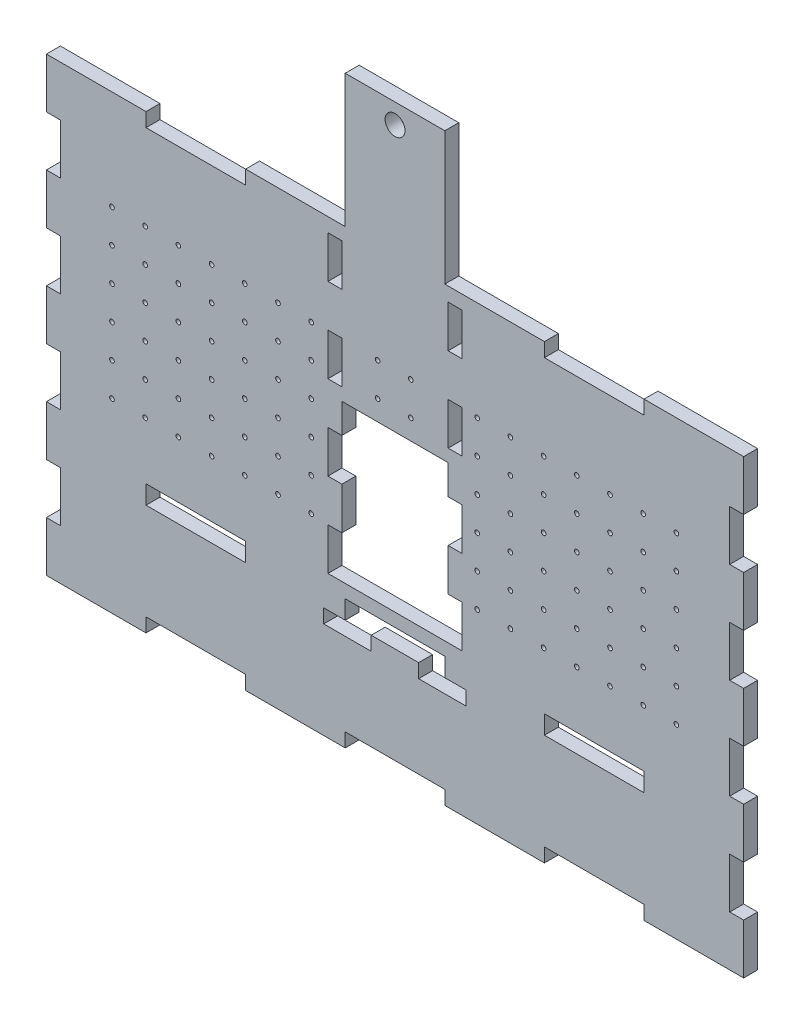
SolidWorks part; units mm, degrees
ref_plane "Front Plane" through (0, 0, 0) normal (0, 0, 1) x (1, 0, 0)
ref_plane "Top Plane" through (0, 0, 0) normal (0, 1, 0) x (1, 0, 0)
ref_plane "Right Plane" through (0, 0, 0) normal (1, 0, 0) x (0, 0, -1)
sketch "Sketch1" plane through (0, 0, 0) normal (0, 0, 1) x (1, 0, 0)
  line L1 (-127.8759, 88.4641) -> (138.8241, 88.4641)
  line L2 (-127.8759, 88.4641) -> (-127.8759, -84.2559)
  line L3 (-127.8759, -84.2559) -> (138.8241, -84.2559)
  line L4 (138.8241, 88.4641) -> (138.8241, -84.2559)
  dimension "D1" = 266.7
  dimension "D2" = 172.72
extrude "Boss-Extrude1" add sketch "Sketch1" along normal blind 5.334
sketch "Sketch2" plane through (0, 0, 5.334) normal (0, 0, 1) x (1, 0, 0)
  line L0 (-127.8759, -84.2559) -> (138.8241, -84.2559) construction
  line L1 (-89.7759, -84.2559) -> (-51.6759, -84.2559)
  line L2 (-89.7759, -84.2559) -> (-89.7759, -78.9219)
  line L3 (-89.7759, -78.9219) -> (-51.6759, -78.9219)
  line L4 (-51.6759, -84.2559) -> (-51.6759, -78.9219)
  line L5 (-89.7759, -78.9219) -> (-127.8759, -78.9219) construction
  line L6 (-13.5759, -84.2559) -> (24.5241, -84.2559)
  line L7 (-13.5759, -84.2559) -> (-13.5759, -78.9219)
  line L8 (-13.5759, -78.9219) -> (24.5241, -78.9219)
  line L9 (24.5241, -84.2559) -> (24.5241, -78.9219)
  line L10 (62.6241, -84.2559) -> (100.7241, -84.2559)
  line L11 (62.6241, -84.2559) -> (62.6241, -78.9219)
  line L12 (62.6241, -78.9219) -> (100.7241, -78.9219)
  line L13 (100.7241, -84.2559) -> (100.7241, -78.9219)
  line L14 (-127.8759, 88.4641) -> (-127.8759, -84.2559) construction
  line L15 (-51.6759, -78.9219) -> (-13.5759, -78.9219) construction
  line L16 (24.5241, -78.9219) -> (62.6241, -78.9219) construction
  line L17 (62.6241, -78.9219) -> (62.364, -79.7896) construction
  line L18 (100.7241, -78.9219) -> (138.8241, -78.9219) construction
  line L19 (138.8241, -84.2559) -> (138.8241, 88.4641) construction
  line L20 (-127.8759, 2.1041) -> (138.8241, 2.1041) construction
  line L21 (100.7241, 88.4641) -> (100.7241, 83.1301)
  line L22 (62.6241, 83.1301) -> (100.7241, 83.1301)
  line L23 (62.6241, 88.4641) -> (62.6241, 83.1301)
  line L24 (24.5241, 88.4641) -> (24.5241, 83.1301)
  line L25 (-13.5759, 83.1301) -> (24.5241, 83.1301)
  line L26 (-13.5759, 88.4641) -> (-13.5759, 83.1301)
  line L27 (-51.6759, 88.4641) -> (-51.6759, 83.1301)
  line L28 (-89.7759, 83.1301) -> (-51.6759, 83.1301)
  line L29 (-89.7759, 88.4641) -> (-89.7759, 83.1301)
  line L30 (62.6241, 88.4641) -> (100.7241, 88.4641)
  line L31 (-13.5759, 88.4641) -> (24.5241, 88.4641)
  line L32 (-89.7759, 88.4641) -> (-51.6759, 88.4641)
  dimension "D1" = 5.334
extrude "Cut-Extrude1" cut sketch "Sketch2" against normal through all
sketch "Sketch5" plane through (0, 0, 5.334) normal (0, 0, 1) x (1, 0, 0)
  line L0 (-51.6759, -34.8224) -> (-13.5759, -34.8224) construction
  line L1 (-89.7759, -34.8224) -> (-51.6759, -34.8224)
  line L2 (-89.7759, -34.8224) -> (-89.7759, -41.9344)
  line L3 (-89.7759, -41.9344) -> (-51.6759, -41.9344)
  line L4 (-51.6759, -34.8224) -> (-51.6759, -41.9344)
  line L5 (-13.5759, -34.8224) -> (24.5241, -34.8224)
  line L6 (-13.5759, -34.8224) -> (-13.5759, -41.9344)
  line L7 (-13.5759, -41.9344) -> (24.5241, -41.9344)
  line L8 (24.5241, -34.8224) -> (24.5241, -41.9344)
  line L9 (62.6241, -34.8224) -> (100.7241, -34.8224)
  line L10 (62.6241, -34.8224) -> (62.6241, -41.9344)
  line L11 (62.6241, -41.9344) -> (100.7241, -41.9344)
  line L12 (100.7241, -34.8224) -> (100.7241, -41.9344)
  line L13 (-51.6759, -41.9344) -> (-13.5759, -41.9344) construction
  line L14 (24.5241, -34.8224) -> (62.6241, -34.8224) construction
  line L15 (24.5241, -41.9344) -> (62.6241, -41.9344) construction
  line L16 (-89.7759, -34.8224) -> (-127.8759, -34.8224) construction
  line L17 (-127.8759, 88.4641) -> (-127.8759, -84.2559) construction
  line L18 (-89.7759, -41.9344) -> (-127.8759, -41.9344) construction
  line L19 (100.7241, -34.8224) -> (138.8241, -34.8224) construction
  line L20 (138.8241, -84.2559) -> (138.8241, 88.4641) construction
  line L21 (100.7241, -41.9344) -> (138.8241, -41.9344) construction
  dimension "D1" = 7.112
extrude "Cut-Extrude3" cut sketch "Sketch5" against normal through all
sketch "Sketch8" plane through (0, 0, 5.334) normal (0, 0, 1) x (1, 0, 0)
  line L0 (-13.5759, -41.9344) -> (24.5241, -41.9344) construction
  line L1 (-21.7977, -47.2684) -> (-3.6478, -47.2684)
  line L2 (-21.7977, -47.2684) -> (-21.7977, -41.9344)
  line L3 (-21.7977, -41.9344) -> (-3.6478, -41.9344)
  line L4 (-3.6478, -47.2684) -> (-3.6478, -41.9344)
  line L5 (-3.6478, -47.2684) -> (14.5022, -47.2684) construction
  line L6 (14.5022, -41.9344) -> (32.6521, -41.9344)
  line L7 (14.5022, -41.9344) -> (14.5022, -47.2684)
  line L8 (14.5022, -47.2684) -> (32.6521, -47.2684)
  line L9 (32.6521, -41.9344) -> (32.6521, -47.2684)
  line L10 (14.5022, -47.2684) -> (14.3218, -49.4005) construction
  line L11 (14.5022, -41.9344) -> (-3.6478, -41.9344) construction
  line L12 (62.6241, -34.8224) -> (62.6241, -41.9344) construction
  line L13 (-51.6759, -41.9344) -> (-51.6759, -34.8224) construction
  dimension "D1" = 5.334
  dimension "D2" = 29.972
  dimension "D3" = 29.8782
extrude "Cut-Extrude6" cut sketch "Sketch8" against normal through all
sketch "Sketch9" plane through (0, 0, 5.334) normal (0, 0, 1) x (1, 0, 0)
  line L0 (-127.8759, 88.4641) -> (-127.8759, -84.2559) construction
  line L1 (-127.8759, -65.0647) -> (-122.5419, -65.0647)
  line L2 (-127.8759, -65.0647) -> (-127.8759, -45.8736)
  line L3 (-127.8759, -45.8736) -> (-122.5419, -45.8736)
  line L4 (-122.5419, -65.0647) -> (-122.5419, -45.8736)
  line L5 (-122.5419, 69.273) -> (-122.5419, 88.4641) construction
  line L6 (-127.8759, -26.6825) -> (-122.5419, -26.6825)
  line L7 (-127.8759, -26.6825) -> (-127.8759, -7.4914)
  line L8 (-127.8759, -7.4914) -> (-122.5419, -7.4914)
  line L9 (-122.5419, -26.6825) -> (-122.5419, -7.4914)
  line L10 (-127.8759, 11.6997) -> (-122.5419, 11.6997)
  line L11 (-127.8759, 11.6997) -> (-127.8759, 30.8908)
  line L12 (-127.8759, 30.8908) -> (-122.5419, 30.8908)
  line L13 (-122.5419, 11.6997) -> (-122.5419, 30.8908)
  line L14 (-127.8759, 50.0819) -> (-122.5419, 50.0819)
  line L15 (-127.8759, 50.0819) -> (-127.8759, 69.273)
  line L16 (-127.8759, 69.273) -> (-122.5419, 69.273)
  line L17 (-122.5419, 50.0819) -> (-122.5419, 69.273)
  line L18 (-89.7759, 88.4641) -> (-127.8759, 88.4641) construction
  line L19 (-122.5419, 50.0819) -> (-122.5419, 30.8908) construction
  line L20 (-122.5419, 11.6997) -> (-122.5419, -7.4914) construction
  line L21 (-122.5419, -26.6825) -> (-122.5419, -45.8736) construction
  line L22 (-122.5419, -65.0647) -> (-122.5419, -84.2559) construction
  line L23 (-127.8759, -84.2559) -> (-89.7759, -84.2559) construction
  line L24 (5.4741, 83.1301) -> (5.4741, -78.9219) construction
  line L25 (-13.5759, 83.1301) -> (24.5241, 83.1301) construction
  line L26 (24.5241, -78.9219) -> (-13.5759, -78.9219) construction
  line L27 (133.4901, -65.0647) -> (133.4901, -84.2559) construction
  line L28 (133.4901, -26.6825) -> (133.4901, -45.8736) construction
  line L29 (133.4901, 11.6997) -> (133.4901, -7.4914) construction
  line L30 (133.4901, 50.0819) -> (133.4901, 30.8908) construction
  line L31 (133.4901, 69.273) -> (133.4901, 88.4641) construction
  line L32 (133.4901, 50.0819) -> (133.4901, 69.273)
  line L33 (138.8241, 69.273) -> (133.4901, 69.273)
  line L34 (138.8241, 50.0819) -> (138.8241, 69.273)
  line L35 (138.8241, 50.0819) -> (133.4901, 50.0819)
  line L36 (133.4901, 11.6997) -> (133.4901, 30.8908)
  line L37 (138.8241, 30.8908) -> (133.4901, 30.8908)
  line L38 (138.8241, 11.6997) -> (138.8241, 30.8908)
  line L39 (138.8241, 11.6997) -> (133.4901, 11.6997)
  line L40 (133.4901, -26.6825) -> (133.4901, -7.4914)
  line L41 (138.8241, -7.4914) -> (133.4901, -7.4914)
  line L42 (138.8241, -26.6825) -> (138.8241, -7.4914)
  line L43 (138.8241, -26.6825) -> (133.4901, -26.6825)
  line L44 (133.4901, -65.0647) -> (133.4901, -45.8736)
  line L45 (138.8241, -45.8736) -> (133.4901, -45.8736)
  line L46 (138.8241, -65.0647) -> (138.8241, -45.8736)
  line L47 (138.8241, -65.0647) -> (133.4901, -65.0647)
  dimension "D1" = 5.334
extrude "Cut-Extrude7" cut sketch "Sketch9" against normal through all
sketch "Sketch10" plane through (0, 88.4641, 0) normal (0, 1, 0) x (1, 0, 0)
  line L1 (24.5241, -5.334) -> (62.6241, -5.334)
  line L2 (24.5241, -5.334) -> (24.5241, 0)
  line L3 (24.5241, 0) -> (62.6241, 0)
  line L4 (62.6241, -5.334) -> (62.6241, 0)
extrude "Boss-Extrude2" add sketch "Sketch10" along normal blind 50.8
sketch "Sketch11" plane through (0, 0, 0) normal (0, 0, -1) x (-1, 0, 0)
  line L0 (-24.5241, 83.1301) -> (-24.5241, 139.2641) construction
  line L1 (-24.5241, 88.4641) -> (-31.1281, 88.4641)
  line L2 (-24.5241, 88.4641) -> (-24.5241, 129.1041)
  line L3 (-24.5241, 129.1041) -> (-31.1281, 129.1041)
  line L4 (-31.1281, 88.4641) -> (-31.1281, 129.1041)
  line L5 (13.5759, 88.4641) -> (51.6759, 88.4641) construction
  dimension "D1" = 6.604
  dimension "D2" = 40.64
  dimension "D3" = 0
extrude "Cut-Extrude8" cut sketch "Sketch11" against normal through all
sketch "Sketch12" plane through (0, 0, 5.334) normal (0, 0, 1) x (1, 0, 0)
  line L0 (62.6241, 139.2641) -> (62.6241, 83.1301) construction
  circle A0 centre (43.5741, 130.4765) radius 3.81
  dimension "D1" = 19.05
extrude "Cut-Extrude9" cut sketch "Sketch12" against normal through all
sketch "Sketch14" plane through (0, 0, 5.334) normal (0, 0, 1) x (1, 0, 0)
  line L0 (-89.7759, 88.4641) -> (-127.8759, 88.4641) construction
  circle A0 centre (-102.7976, 50.3641) radius 0.889
  circle A1 centre (-90.0976, 50.3641) radius 0.889
  circle A2 centre (-77.3976, 50.3641) radius 0.889
  circle A3 centre (-64.6976, 50.3641) radius 0.889
  circle A4 centre (-51.9976, 50.3641) radius 0.889
  circle A5 centre (-39.2976, 50.3641) radius 0.889
  circle A6 centre (-26.5976, 50.3641) radius 0.889
  circle A8 centre (-1.1976, 50.3641) radius 0.889
  circle A9 centre (11.5024, 50.3641) radius 0.889
  circle A11 centre (36.9024, 50.3641) radius 0.889
  circle A12 centre (49.6024, 50.3641) radius 0.889
  circle A13 centre (62.3024, 50.3641) radius 0.889
  circle A14 centre (75.0024, 50.3641) radius 0.889
  circle A15 centre (87.7024, 50.3641) radius 0.889
  circle A16 centre (100.4024, 50.3641) radius 0.889
  circle A17 centre (113.1024, 50.3641) radius 0.889
  circle A18 centre (-102.7976, 37.6641) radius 0.889
  circle A19 centre (-90.0976, 37.6641) radius 0.889
  circle A20 centre (-77.3976, 37.6641) radius 0.889
  circle A21 centre (-64.6976, 37.6641) radius 0.889
  circle A22 centre (-51.9976, 37.6641) radius 0.889
  circle A23 centre (-39.2976, 37.6641) radius 0.889
  circle A24 centre (-26.5976, 37.6641) radius 0.889
  circle A26 centre (-1.1976, 37.6641) radius 0.889
  circle A27 centre (11.5024, 37.6641) radius 0.889
  circle A29 centre (36.9024, 37.6641) radius 0.889
  circle A30 centre (49.6024, 37.6641) radius 0.889
  circle A31 centre (62.3024, 37.6641) radius 0.889
  circle A32 centre (75.0024, 37.6641) radius 0.889
  circle A33 centre (87.7024, 37.6641) radius 0.889
  circle A34 centre (100.4024, 37.6641) radius 0.889
  circle A35 centre (113.1024, 37.6641) radius 0.889
  circle A36 centre (-102.7976, 24.9641) radius 0.889
  circle A37 centre (-90.0976, 24.9641) radius 0.889
  circle A38 centre (-77.3976, 24.9641) radius 0.889
  circle A39 centre (-64.6976, 24.9641) radius 0.889
  circle A40 centre (-51.9976, 24.9641) radius 0.889
  circle A41 centre (-39.2976, 24.9641) radius 0.889
  circle A42 centre (-26.5976, 24.9641) radius 0.889
  circle A44 centre (-1.1976, 24.9641) radius 0.889
  circle A45 centre (11.5024, 24.9641) radius 0.889
  circle A47 centre (36.9024, 24.9641) radius 0.889
  circle A48 centre (49.6024, 24.9641) radius 0.889
  circle A49 centre (62.3024, 24.9641) radius 0.889
  circle A50 centre (75.0024, 24.9641) radius 0.889
  circle A51 centre (87.7024, 24.9641) radius 0.889
  circle A52 centre (100.4024, 24.9641) radius 0.889
  circle A53 centre (113.1024, 24.9641) radius 0.889
  circle A54 centre (-102.7976, 12.2641) radius 0.889
  circle A55 centre (-90.0976, 12.2641) radius 0.889
  circle A56 centre (-77.3976, 12.2641) radius 0.889
  circle A57 centre (-64.6976, 12.2641) radius 0.889
  circle A58 centre (-51.9976, 12.2641) radius 0.889
  circle A59 centre (-39.2976, 12.2641) radius 0.889
  circle A60 centre (-26.5976, 12.2641) radius 0.889
  circle A65 centre (36.9024, 12.2641) radius 0.889
  circle A66 centre (49.6024, 12.2641) radius 0.889
  circle A67 centre (62.3024, 12.2641) radius 0.889
  circle A68 centre (75.0024, 12.2641) radius 0.889
  circle A69 centre (87.7024, 12.2641) radius 0.889
  circle A70 centre (100.4024, 12.2641) radius 0.889
  circle A71 centre (113.1024, 12.2641) radius 0.889
  circle A72 centre (-102.7976, -0.4359) radius 0.889
  circle A73 centre (-90.0976, -0.4359) radius 0.889
  circle A74 centre (-77.3976, -0.4359) radius 0.889
  circle A75 centre (-64.6976, -0.4359) radius 0.889
  circle A76 centre (-51.9976, -0.4359) radius 0.889
  circle A77 centre (-39.2976, -0.4359) radius 0.889
  circle A78 centre (-26.5976, -0.4359) radius 0.889
  circle A79 centre (-13.8976, -0.4359) radius 0.889
  circle A80 centre (-1.1976, -0.4359) radius 0.889
  circle A81 centre (11.5024, -0.4359) radius 0.889
  circle A82 centre (24.2024, -0.4359) radius 0.889
  circle A83 centre (36.9024, -0.4359) radius 0.889
  circle A84 centre (49.6024, -0.4359) radius 0.889
  circle A85 centre (62.3024, -0.4359) radius 0.889
  circle A86 centre (75.0024, -0.4359) radius 0.889
  circle A87 centre (87.7024, -0.4359) radius 0.889
  circle A88 centre (100.4024, -0.4359) radius 0.889
  circle A89 centre (113.1024, -0.4359) radius 0.889
  circle A90 centre (-102.7976, -13.1359) radius 0.889
  circle A91 centre (-90.0976, -13.1359) radius 0.889
  circle A92 centre (-77.3976, -13.1359) radius 0.889
  circle A93 centre (-64.6976, -13.1359) radius 0.889
  circle A94 centre (-51.9976, -13.1359) radius 0.889
  circle A95 centre (-39.2976, -13.1359) radius 0.889
  circle A96 centre (-26.5976, -13.1359) radius 0.889
  circle A97 centre (-13.8976, -13.1359) radius 0.889
  circle A98 centre (-1.1976, -13.1359) radius 0.889
  circle A99 centre (11.5024, -13.1359) radius 0.889
  circle A100 centre (24.2024, -13.1359) radius 0.889
  circle A101 centre (36.9024, -13.1359) radius 0.889
  circle A102 centre (49.6024, -13.1359) radius 0.889
  circle A103 centre (62.3024, -13.1359) radius 0.889
  circle A104 centre (75.0024, -13.1359) radius 0.889
  circle A105 centre (87.7024, -13.1359) radius 0.889
  circle A106 centre (100.4024, -13.1359) radius 0.889
  circle A107 centre (113.1024, -13.1359) radius 0.889
  circle A108 centre (-1.1976, 12.2641) radius 0.889 [skipped]
  circle A110 centre (11.5024, 12.2641) radius 0.889 [skipped]
  circle A116 centre (24.2024, 50.3641) radius 0.889 [skipped]
  circle A117 centre (-13.8976, 50.3641) radius 0.889 [skipped]
  dimension "D1" = 18
  dimension "D2" = 38.1
  dimension "D4" = 1.778
  dimension "D3" = 6
extrude "Cut-Extrude11" cut sketch "Sketch14" against normal through all
sketch "Sketch15" plane through (0, 0, 5.334) normal (0, 0, 1) x (1, 0, 0)
  line L1 (31.1281, 129.1041) -> (24.5241, 129.1041)
  line L2 (31.1281, 129.1041) -> (31.1281, 139.2641)
  line L3 (31.1281, 139.2641) -> (24.5241, 139.2641)
  line L4 (24.5241, 129.1041) -> (24.5241, 139.2641)
extrude "Cut-Extrude12" cut sketch "Sketch15" against normal through all
sketch "Sketch16" plane through (0, 0, 5.334) normal (0, 0, 1) x (1, 0, 0)
  line L0 (5.4741, 83.1301) -> (5.4741, -78.9219) construction
  line L1 (-14.8459, 29.9476) -> (25.7941, 29.9476)
  line L2 (-14.8459, 29.9476) -> (-14.8459, -29.7424)
  line L3 (-14.8459, -29.7424) -> (25.7941, -29.7424)
  line L4 (25.7941, 29.9476) -> (25.7941, -29.7424)
  line L5 (-13.5759, 83.1301) -> (24.5241, 83.1301) construction
  line L6 (24.5241, -78.9219) -> (-13.5759, -78.9219) construction
  line L7 (24.5241, -34.8224) -> (-13.5759, -34.8224) construction
  dimension "D1" = 59.69
  dimension "D2" = 40.64
  dimension "D3" = 20.32
  dimension "D4" = 5.08
extrude "Cut-Extrude13" cut sketch "Sketch16" against normal through all
sketch "Sketch17" plane through (0, 0, 5.334) normal (0, 0, 1) x (1, 0, 0)
  line L0 (-14.8459, 29.9476) -> (-14.8459, -29.7424) construction
  line L1 (-14.8459, -29.7424) -> (-20.1799, -29.7424)
  line L2 (-14.8459, -29.7424) -> (-14.8459, -13.6178)
  line L3 (-14.8459, -13.6178) -> (-20.1799, -13.6178)
  line L4 (-20.1799, -29.7424) -> (-20.1799, -13.6178)
  line L5 (-14.8459, 2.5069) -> (-20.1799, 2.5069)
  line L6 (-14.8459, 2.5069) -> (-14.8459, 18.6315)
  line L7 (-14.8459, 18.6315) -> (-20.1799, 18.6315)
  line L8 (-20.1799, 2.5069) -> (-20.1799, 18.6315)
  line L9 (-20.1799, -13.6178) -> (-20.1799, 2.5069) construction
  line L10 (-20.1799, 50.8808) -> (-14.8459, 50.8808)
  line L11 (-20.1799, 50.8808) -> (-20.1799, 34.7562)
  line L12 (-20.1799, 34.7562) -> (-14.8459, 34.7562)
  line L13 (-14.8459, 50.8808) -> (-14.8459, 34.7562)
  line L14 (-20.1799, 67.0055) -> (-14.8459, 67.0055)
  line L15 (-20.1799, 67.0055) -> (-20.1799, 83.1301)
  line L16 (-20.1799, 83.1301) -> (-14.8459, 83.1301)
  line L17 (-14.8459, 67.0055) -> (-14.8459, 83.1301)
  line L18 (-20.1799, 18.6315) -> (-20.1799, 34.7562) construction
  line L19 (-20.1799, 67.0055) -> (-20.1799, 50.8808) construction
  line L20 (5.4741, 83.1301) -> (5.4741, -78.9219) construction
  line L21 (-13.5759, 83.1301) -> (24.5241, 83.1301) construction
  line L22 (24.5241, -78.9219) -> (-13.5759, -78.9219) construction
  line L23 (31.1281, 67.0055) -> (31.1281, 50.8808) construction
  line L24 (31.1281, 18.6315) -> (31.1281, 34.7562) construction
  line L25 (31.1281, -13.6178) -> (31.1281, 2.5069) construction
  line L26 (25.7941, 67.0055) -> (25.7941, 83.1301)
  line L27 (31.1281, 83.1301) -> (25.7941, 83.1301)
  line L28 (31.1281, 67.0055) -> (31.1281, 83.1301)
  line L29 (31.1281, 67.0055) -> (25.7941, 67.0055)
  line L30 (25.7941, 50.8808) -> (25.7941, 34.7562)
  line L31 (31.1281, 34.7562) -> (25.7941, 34.7562)
  line L32 (31.1281, 50.8808) -> (31.1281, 34.7562)
  line L33 (31.1281, 50.8808) -> (25.7941, 50.8808)
  line L34 (31.1281, 2.5069) -> (31.1281, 18.6315)
  line L35 (25.7941, 18.6315) -> (31.1281, 18.6315)
  line L36 (25.7941, 2.5069) -> (25.7941, 18.6315)
  line L37 (25.7941, 2.5069) -> (31.1281, 2.5069)
  line L38 (31.1281, -29.7424) -> (31.1281, -13.6178)
  line L39 (25.7941, -13.6178) -> (31.1281, -13.6178)
  line L40 (25.7941, -29.7424) -> (25.7941, -13.6178)
  line L41 (25.7941, -29.7424) -> (31.1281, -29.7424)
  dimension "D1" = 0
  dimension "D2" = 5.334
  dimension "D3" = 5.334
  dimension "D4" = 5.334
extrude "Cut-Extrude14" cut sketch "Sketch17" against normal through all
sketch "Sketch18" plane through (0, 0, 5.334) normal (0, 0, 1) x (1, 0, 0)
  line L0 (24.5241, 83.1301) -> (24.5241, 148.9274) construction
  line L1 (31.1281, 139.2641) -> (62.6241, 139.2641) construction
  line L2 (-13.5759, 83.1301) -> (24.5241, 83.1301)
  line L3 (-13.5759, 83.1301) -> (-13.5759, 139.2641)
  line L4 (-13.5759, 139.2641) -> (24.5241, 139.2641)
  line L5 (24.5241, 83.1301) -> (24.5241, 139.2641)
  dimension "D1" = 0
extrude "Boss-Extrude3" add sketch "Sketch18" against normal blind 5.334
sketch "Sketch19" plane through (0, 0, 5.334) normal (0, 0, 1) x (1, 0, 0)
  line L1 (31.1281, 88.4641) -> (65.8849, 88.4641)
  line L2 (31.1281, 88.4641) -> (31.1281, 143.4078)
  line L3 (31.1281, 143.4078) -> (65.8849, 143.4078)
  line L4 (65.8849, 88.4641) -> (65.8849, 143.4078)
extrude "Cut-Extrude15" cut sketch "Sketch19" against normal through all
sketch "Sketch20" plane through (0, 0, 5.334) normal (0, 0, 1) x (1, 0, 0)
  line L0 (5.4741, 139.2641) -> (5.4741, 29.9476) construction
  line L1 (24.5241, 139.2641) -> (-13.5759, 139.2641) construction
  line L2 (25.7941, 29.9476) -> (-14.8459, 29.9476) construction
  circle A0 centre (5.4741, 131.6441) radius 3.81
  dimension "D1" = 7.62
  dimension "D3" = 7.62
  dimension "D2" = 0
extrude "Cut-Extrude16" cut sketch "Sketch20" against normal through all contours A0
equation "\"MDF\"= .21in"
equation "\"Foamcore\"= .13in"
equation "\"Gmaterial\"= \"MDF\""
equation "\"D1@Boss-Extrude1\"=\"MDF\""
equation "\"D1@Sketch2\"=\"MDF\""
equation "\"D1@Sketch5\"=\"MDF\"+0.07"
equation "\"D1@Sketch8\"=\"MDF\""
equation "\"D1@Sketch9\"=\"MDF\""
equation "\"D1@Sketch11\"=\"MDF\"+.05"
equation "\"D2@Sketch17\"=\"MDF\""
equation "\"D3@Sketch17\"=\"MDF\""
equation "\"D4@Sketch17\"=\"MDF\""
equation "\"D1@Boss-Extrude3\"=\"MDF\""
